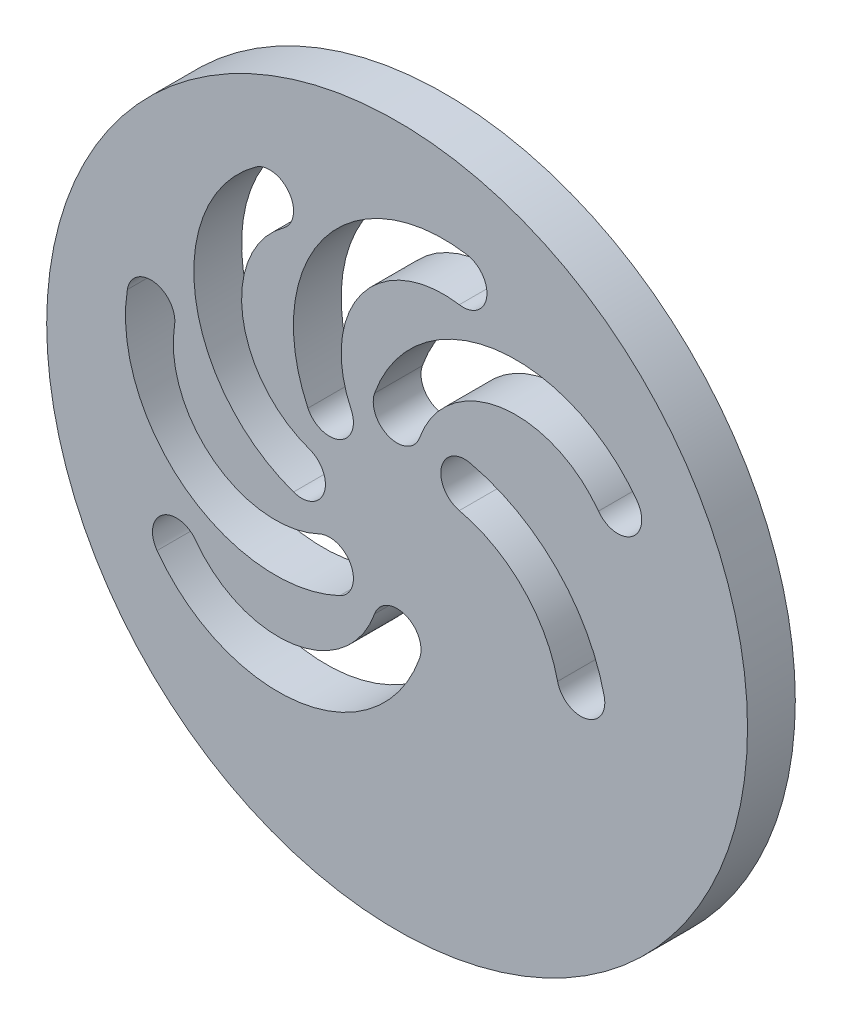
SolidWorks part; units mm, degrees
ref_plane "Front Plane" through (0, 0, 0) normal (0, 0, 1) x (1, 0, 0)
ref_plane "Top Plane" through (0, 0, 0) normal (0, 1, 0) x (1, 0, 0)
ref_plane "Right Plane" through (0, 0, 0) normal (1, 0, 0) x (0, 0, -1)
sketch "Sketch1" plane through (0, 0, 0) normal (0, 0, 1) x (1, 0, 0)
  line L0 (0, 60.505) -> (0, -60.505) construction
  line L1 (-16.0502, -9.2666) -> (16.0502, 9.2666) construction
  line L2 (0, 0) -> (0, 9.525) construction
  line L3 (0, 0) -> (6.7352, 6.7352) construction
  line L4 (0, 9.525) -> (0, 34.925) construction
  line L5 (0, 0) -> (18.3186, -4.9085) construction
  circle A0 centre (0, 0) radius 34.925
  arc A1 (2.2439, 8.7279) -> (-2.2439, 10.3221) centre (0, 9.525) cw
  arc A2 (-2.2439, 10.3221) -> (23.9239, 14.0991) centre (11.8344, 5.3212) cw
  arc A3 (23.9239, 14.0991) -> (20.0701, 11.3009) centre (21.997, 12.7) cw
  arc A4 (20.0701, 11.3009) -> (2.2439, 8.7279) centre (11.8344, 5.3212) ccw
  arc A25 (2.2439, -10.3221) -> (-23.9239, -14.0991) centre (-11.8344, -5.3212) cw
  arc A26 (-2.2439, -8.7279) -> (2.2439, -10.3221) centre (0, -9.525) cw
  arc A27 (-20.0701, -11.3009) -> (-2.2439, -8.7279) centre (-11.8344, -5.3212) ccw
  arc A28 (-23.9239, -14.0991) -> (-20.0701, -11.3009) centre (-21.997, -12.7) cw
  arc A29 (-5.7121, -8.8855) -> (-26.8863, 6.9472) centre (-12.1309, 4.6055) cw
  arc A30 (-7.7582, -4.5849) -> (-5.7121, -8.8855) centre (-6.7352, -6.7352) cw
  arc A31 (-22.1827, 6.2008) -> (-7.7582, -4.5849) centre (-12.1309, 4.6055) ccw
  arc A32 (-26.8863, 6.9472) -> (-22.1827, 6.2008) centre (-24.5345, 6.574) cw
  arc A33 (-10.3221, -2.2439) -> (-14.0991, 23.9239) centre (-5.3212, 11.8344) cw
  arc A34 (-8.7279, 2.2439) -> (-10.3221, -2.2439) centre (-9.525, 0) cw
  arc A35 (-11.3009, 20.0701) -> (-8.7279, 2.2439) centre (-5.3212, 11.8344) ccw
  arc A36 (-14.0991, 23.9239) -> (-11.3009, 20.0701) centre (-12.7, 21.997) cw
  arc A37 (-8.8855, 5.7121) -> (6.9472, 26.8863) centre (4.6055, 12.1309) cw
  arc A38 (-4.5849, 7.7582) -> (-8.8855, 5.7121) centre (-6.7352, 6.7352) cw
  arc A39 (6.2008, 22.1827) -> (-4.5849, 7.7582) centre (4.6055, 12.1309) ccw
  arc A40 (6.9472, 26.8863) -> (6.2008, 22.1827) centre (6.574, 24.5345) cw
  arc A41 (5.7121, 8.8855) -> (26.8863, -6.9472) centre (12.1309, -4.6055) cw [skipped]
  arc A42 (7.7582, 4.5849) -> (5.7121, 8.8855) centre (6.7352, 6.7352) cw [skipped]
  arc A43 (22.1827, -6.2008) -> (7.7582, 4.5849) centre (12.1309, -4.6055) ccw [skipped]
  arc A44 (26.8863, -6.9472) -> (22.1827, -6.2008) centre (24.5345, -6.574) cw [skipped]
  circle A53 centre (0, 0) radius 9.525 construction
  arc A54 (6.201, 4.4146) -> (7.2694, 9.0558) centre (6.7352, 6.7352) cw
  arc A55 (7.2694, 9.0558) -> (20.6419, -4.3863) centre (3.2768, -8.2889) cw
  arc A57 (15.9953, -5.4306) -> (6.201, 4.4146) centre (3.2768, -8.2889) ccw
  arc A58 (15.9953, -5.4306) -> (20.6419, -4.3863) centre (18.3186, -4.9085) ccw
  arc A60 (10.3221, 2.2439) -> (14.0991, -23.9239) centre (5.3212, -11.8344) cw [skipped]
  arc A61 (8.7279, -2.2439) -> (10.3221, 2.2439) centre (9.525, 0) cw [skipped]
  arc A62 (11.3009, -20.0701) -> (8.7279, -2.2439) centre (5.3212, -11.8344) ccw [skipped]
  arc A63 (14.0991, -23.9239) -> (11.3009, -20.0701) centre (12.7, -21.997) cw [skipped]
  arc A64 (8.8855, -5.7121) -> (-6.9472, -26.8863) centre (-4.6055, -12.1309) cw [skipped]
  arc A65 (4.5849, -7.7582) -> (8.8855, -5.7121) centre (6.7352, -6.7352) cw [skipped]
  arc A66 (-6.2008, -22.1827) -> (4.5849, -7.7582) centre (-4.6055, -12.1309) ccw [skipped]
  arc A67 (-6.9472, -26.8863) -> (-6.2008, -22.1827) centre (-6.574, -24.5345) cw [skipped]
  point P6 (0, 0)
  point P17 (0, 0)
  dimension "D1" = 9.525
  dimension "D3" = 60
  dimension "D4" = 25.4
  dimension "D2" = 2.3813
  dimension "D7" = 25.4
  dimension "D6" = 45
  dimension "D8" = 60
  dimension "D5" = 8
extrude "Boss-Extrude1" add sketch "Sketch1" along normal blind 4.7625
ref_axis "Axis1" through (0, 0, 0) along (0, 0, 1)
equation "\"slot-end-angle\"=60"
equation "\"D3@Sketch1\"=\"slot-end-angle\""
equation "\"slot-spacing-angle\"=60"
equation "\"slot-gap\"=0.01"
equation "\"pulley-thickness\"=0.25"
equation "\"pin-diameter\"=2*\"slot-radius\"-2*\"slot-gap\""
equation "\"slot-radius\"=3/32"
equation "\"D2@Sketch1\"=\"slot-radius\""
equation "\"vert-line-length\"=2.0in"
equation "\"disc-thickness\"=0.1875in"
equation "\"D1@Boss-Extrude1\"=\"disc-thickness\""
equation "\"center-distance\"=0.375in"
equation "\"D1@Sketch1\"=\"center-distance\""
equation "\"slot-to-disc-OD\"=1.0in"
equation "\"D7@Sketch1\"=\"slot-to-disc-OD\""
equation "\"number-slots\"=8"
equation "\"D5@Sketch1\"=\"number-slots\""
equation "\"slot-seed-spacing\"=360/\"number-slots\""
equation "\"D6@Sketch1\"=\"slot-seed-spacing\""
